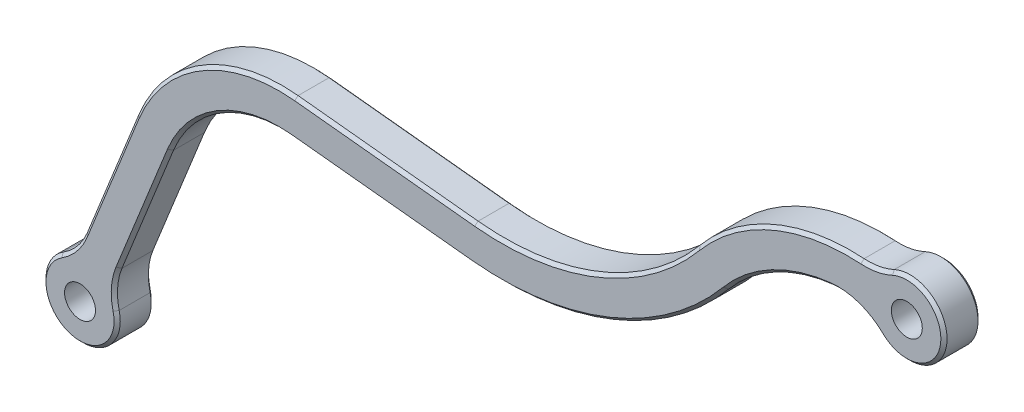
SolidWorks part; units mm, degrees
note: The reader was unsure of these and kept them because the rebuilt part matched: shared geometry of "Sketch1<3>".
other "DetailItem1"
other "DetailItem2"
material "Titanium Ti-8Mn, Annealed"
ref_plane "Спереди" through (0, 0, 0) normal (0, 0, 1) x (1, 0, 0)
ref_plane "Сверху" through (0, 0, 0) normal (0, 1, 0) x (1, 0, 0)
ref_plane "Справа" through (0, 0, 0) normal (1, 0, 0) x (0, 0, -1)
other "Configuration Table"
sketch "Sketch1" plane through (0, 0, 0) normal (0, 0, 1) x (1, 0, 0)
  line L0 (32.4057, 20.4925) -> (17.8642, 22.0056)
  line L1 (30.9283, 23.6624) -> (21.4794, 24.6456) construction
  line L2 (6.5582, 15.1948) -> (0.6537, 0.5285)
  circle A0 centre (0.6537, 0.5285) radius 3 construction
  circle A1 centre (0.6537, 0.5285) radius 3
  arc A3 (70.3356, 33.4669) -> (64.5425, 31.9047) centre (67.439, 32.6858) ccw construction
  circle A4 centre (67.439, 32.6858) radius 3
  arc A5 (32.4057, 20.4925) -> (51.6437, 28.3114) centre (34.6903, 42.4479) ccw
  arc A6 (51.6437, 28.3114) -> (67.439, 32.6858) centre (62.7003, 19.0919) cw
  arc A7 (17.8642, 22.0056) -> (6.5582, 15.1948) centre (16.7294, 11.1) ccw
  arc A9 (27.3821, 20.9871) -> (24.3988, 21.2975) centre (25.8934, 21.1702) ccw construction
  arc A11 (60.1153, 31.1852) -> (49.5038, 26.4206) centre (60.4973, 16.1355) ccw construction
extrude "Extrude-Thin1" add sketch "Sketch1" along normal blind 3 thin contours A5 L0 | L0 A7 L2
extrude "Boss-Extrude1" add sketch "Sketch1<3>" along normal through all
sketch "Sketch1<3>" plane through (0, 0, 0) normal (0, 0, 1) x (1, 0, 0) same geometry as "Sketch1"
fillet "Fillet1" radius 5 4 edges at (3.0154, 2.3784, 1.5) (0.2325, 3.4988, 1.5) (64.5567, 31.8537, 1.5) (65.2872, 34.7761, 1.5)
hole_wizard "Ø2.5mm Dowel Hole1" positions "Sketch2" profile "Sketch3" hole size "Ø2.5" standard "ISO" end condition through all
sketch "Sketch2" plane through (0, 0, 3) normal (0, 0, 1) x (1, 0, 0)
  arc A0 (65.35, 30.5326) -> (66.1766, 35.4072) centre (67.439, 32.6858) ccw construction
  arc A1 (65.35, 30.5326) -> (66.1766, 35.4072) centre (67.439, 32.6858) ccw
  point P0 (67.439, 32.6858)
  point P2 (0.6537, 0.5285)
sketch "Sketch3" plane through (67.439, 32.6858, 3) normal (1, 0, 0) x (0, -1, 0)
  line L0 (0, 0) -> (0, 3)
  line L1 (0, 3) -> (1.25, 3)
  line L2 (1.25, 3) -> (1.25, 0)
  line L5 (1.25, 0) -> (0, 0)
  line L11 (0, -6.35) -> (0, 107.95) construction
  dimension "Thru Hole Dia." = 2.5
  dimension "Thru Hole Depth" = 3
chamfer "Chamfer1" distance 0.25 angle 45 32 edges at (43.5664, 20.6088, 0) (56.6235, 30.4666, 0) (24.9797, 19.7571, 0) (63.4997, 31.6705, 0) (11.8456, 19.2071, 0) (70.3968, 32.1842, 3) (70.3968, 32.1842, 0) (5.8683, 9.4646, 0) (64.9889, 35.0276, 0) (3.4379, 2.7848, 0) (56.4366, 33.7019, 0) (-0.4667, -2.2544, 0) (-0.4667, -2.2544, 3) (42.4368, 23.3881, 0) (0.2094, 4.0845, 0) (25.2902, 22.741, 0) (3.0853, 10.585, 0) (10.2975, 21.7769, 0) (43.5664, 20.6088, 3) (56.6235, 30.4666, 3) (24.9797, 19.7571, 3) (63.4997, 31.6705, 3) (11.8456, 19.2071, 3) (5.8683, 9.4646, 3) (64.9889, 35.0276, 3) (3.4379, 2.7848, 3) (56.4366, 33.7019, 3) (42.4368, 23.3881, 3) (0.2094, 4.0845, 3) (25.2902, 22.741, 3) (3.0853, 10.585, 3) (10.2975, 21.7769, 3)
